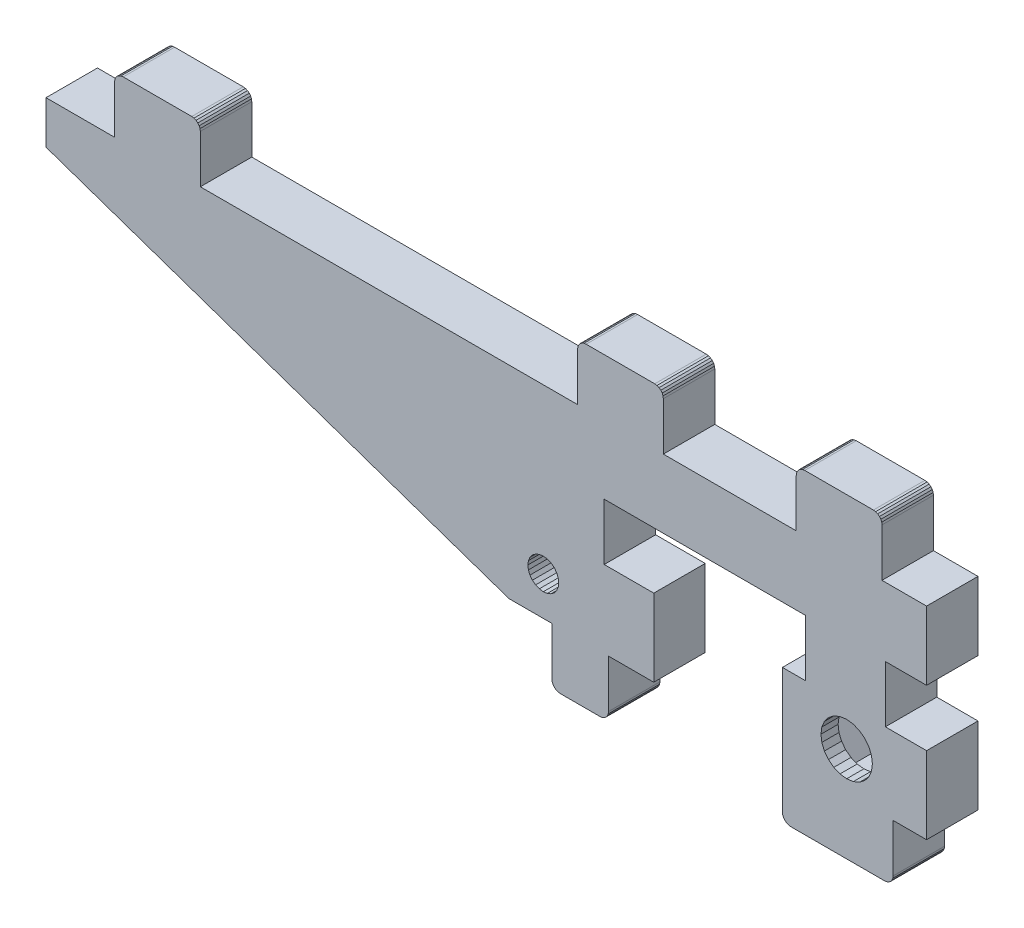
SolidWorks part; units mm, degrees
material "Maple"
ref_plane "Front Plane" through (0, 0, 0) normal (0, 0, 1) x (1, 0, 0)
ref_plane "Top Plane" through (0, 0, 0) normal (0, 1, 0) x (1, 0, 0)
ref_plane "Right Plane" through (0, 0, 0) normal (1, 0, 0) x (0, 0, -1)
sketch "Sketch1" plane through (0, 0, 0) normal (0, 0, 1) x (1, 0, 0)
  line L2259 (-418.414, -391.9409) -> (-418.7137, -392.6645)
  line L2260 (-501.1985, -368.7409) -> (-501.1985, -374.3409)
  line L2261 (-500.4573, -367.775) -> (-500.1985, -367.7409)
  line L2262 (-438.316, -397.9409) -> (-438.316, -388.9409)
  line L2263 (-451.1985, -391.6409) -> (-450.7326, -391.7022)
  line L2264 (-437.3325, -368.2409) -> (-437.4914, -368.0338)
  line L2265 (-451.6644, -391.7022) -> (-451.1985, -391.6409)
  line L2266 (-452.0985, -391.8821) -> (-451.6644, -391.7022)
  line L2267 (-406.5002, -397.9409) -> (-406.5002, -388.9447)
  line L2268 (-509.1985, -374.3409) -> (-509.1985, -379.3409)
  line L2269 (-452.7573, -394.3409) -> (-452.9372, -393.9068)
  line L2270 (-418.7137, -394.2174) -> (-418.414, -394.9409)
  line L2271 (-449.4598, -392.975) -> (-449.3985, -393.4409)
  line L2272 (-410.3985, -397.9409) -> (-410.3985, -403.5409)
  line L2273 (-450.7326, -395.1796) -> (-451.1985, -395.2409)
  line L2274 (-452.0985, -394.9998) -> (-452.4713, -394.7137)
  line L2275 (-449.4598, -393.9068) -> (-449.6396, -394.3409)
  line L2276 (-411.3037, -388.9409) -> (-411.2985, -382.3409)
  line L2277 (-411.2985, -382.3409) -> (-406.5002, -382.3447)
  line L2278 (-450.1985, -397.9409) -> (-455.1985, -397.9409)
  line L2279 (-437.1985, -374.3409) -> (-421.6985, -374.3409)
  line L2280 (-491.1985, -368.7409) -> (-491.1985, -374.3409)
  line L2281 (-491.1985, -374.3409) -> (-447.1985, -374.3409)
  line L2282 (-413.2179, -388.9409) -> (-418.414, -388.9409)
  line L2283 (-406.5002, -388.9447) -> (-411.3037, -388.9409)
  line L2284 (-422.8108, -404.4069) -> (-423.0179, -404.248)
  line L2285 (-443.5985, -397.9409) -> (-438.316, -397.9409)
  line L2286 (-420.5985, -388.9409) -> (-420.5985, -382.3409)
  line L2287 (-509.1985, -374.3409) -> (-501.1985, -374.3409)
  line L2288 (-443.5985, -403.5409) -> (-443.5985, -397.9409)
  line L2289 (-443.5985, -403.5409) -> (-443.6326, -403.7997)
  line L2290 (-443.6326, -403.7997) -> (-443.7325, -404.0409)
  line L2291 (-443.7325, -404.0409) -> (-443.8914, -404.248)
  line L2292 (-413.2179, -397.9409) -> (-410.6198, -393.4409)
  line L2293 (-412.9182, -392.6645) -> (-413.2179, -391.9409)
  line L2294 (-452.4713, -394.7137) -> (-452.7573, -394.3409)
  line L2295 (-421.6985, -368.7409) -> (-421.6644, -368.4821)
  line L2296 (-410.5325, -404.0409) -> (-410.6914, -404.248)
  line L2297 (-410.6914, -404.248) -> (-410.8985, -404.4069)
  line L2298 (-410.8985, -404.4069) -> (-411.1397, -404.5068)
  line L2299 (-492.1985, -367.7409) -> (-500.1985, -367.7409)
  line L2300 (-411.1397, -404.5068) -> (-411.3985, -404.5409)
  line L2301 (-447.0645, -368.2409) -> (-446.9056, -368.0338)
  line L2302 (-446.9056, -368.0338) -> (-446.6985, -367.8749)
  line L2303 (-418.414, -388.9409) -> (-421.0121, -393.4409)
  line L2304 (-421.0121, -393.4409) -> (-418.414, -397.9409)
  line L2305 (-418.414, -397.9409) -> (-413.2179, -397.9409)
  line L2306 (-410.6198, -393.4409) -> (-413.2179, -388.9409)
  line L2307 (-418.414, -394.9409) -> (-417.9373, -395.5622)
  line L2308 (-417.9373, -391.3196) -> (-418.414, -391.9409)
  line L2309 (-415.816, -390.4409) -> (-416.5924, -390.5431)
  line L2310 (-415.0395, -390.5431) -> (-415.816, -390.4409)
  line L2311 (-413.2179, -391.9409) -> (-413.6946, -391.3196)
  line L2312 (-413.2179, -394.9409) -> (-412.9182, -394.2174)
  line L2313 (-413.6946, -395.5622) -> (-413.2179, -394.9409)
  line L2314 (-412.4397, -367.775) -> (-412.1985, -367.8749)
  line L2315 (-412.1985, -367.8749) -> (-411.9914, -368.0338)
  line L2316 (-411.9914, -368.0338) -> (-411.8325, -368.2409)
  line L2317 (-411.8325, -368.2409) -> (-411.7326, -368.4821)
  line L2318 (-411.7326, -368.4821) -> (-411.6985, -368.7409)
  line L2319 (-501.1985, -368.7409) -> (-501.1644, -368.4821)
  line L2320 (-452.9372, -392.975) -> (-452.7573, -392.5409)
  line L2321 (-423.0179, -404.248) -> (-423.1768, -404.0409)
  line L2322 (-423.1768, -404.0409) -> (-423.2767, -403.7997)
  line L2323 (-423.2767, -403.7997) -> (-423.3108, -403.5409)
  line L2324 (-437.2326, -368.4821) -> (-437.3325, -368.2409)
  line L2325 (-437.1985, -368.7409) -> (-437.2326, -368.4821)
  line L2326 (-437.1985, -368.7409) -> (-437.1985, -374.3409)
  line L2327 (-421.5645, -368.2409) -> (-421.4056, -368.0338)
  line L2328 (-421.4056, -368.0338) -> (-421.1985, -367.8749)
  line L2329 (-449.9056, -404.248) -> (-449.6985, -404.4069)
  line L2330 (-449.6985, -404.4069) -> (-449.4573, -404.5068)
  line L2331 (-449.1985, -404.5409) -> (-444.5985, -404.5409)
  line L2332 (-449.4573, -404.5068) -> (-449.1985, -404.5409)
  line L2333 (-437.4914, -368.0338) -> (-437.6985, -367.8749)
  line L2334 (-437.6985, -367.8749) -> (-437.9397, -367.775)
  line L2335 (-438.1985, -367.7409) -> (-446.1985, -367.7409)
  line L2336 (-437.9397, -367.775) -> (-438.1985, -367.7409)
  line L2337 (-452.9985, -393.4409) -> (-452.9372, -392.975)
  line L2338 (-444.0985, -382.3409) -> (-444.0985, -388.9409)
  line L2339 (-451.6644, -395.1796) -> (-452.0985, -394.9998)
  line L2340 (-452.9372, -393.9068) -> (-452.9985, -393.4409)
  line L2341 (-450.7326, -391.7022) -> (-450.2985, -391.8821)
  line L2342 (-509.1985, -379.3409) -> (-455.1985, -397.9409)
  line L2343 (-447.1985, -368.7409) -> (-447.1985, -374.3409)
  line L2344 (-447.1985, -368.7409) -> (-447.1644, -368.4821)
  line L2345 (-447.1644, -368.4821) -> (-447.0645, -368.2409)
  line L2346 (-422.3108, -404.5409) -> (-422.5696, -404.5068)
  line L2347 (-422.5696, -404.5068) -> (-422.8108, -404.4069)
  line L2348 (-423.3108, -403.5409) -> (-423.3108, -388.9409)
  line L2349 (-492.1985, -367.7409) -> (-491.9397, -367.775)
  line L2350 (-491.9397, -367.775) -> (-491.6985, -367.8749)
  line L2351 (-491.6985, -367.8749) -> (-491.4914, -368.0338)
  line L2352 (-491.4914, -368.0338) -> (-491.3325, -368.2409)
  line L2353 (-491.3325, -368.2409) -> (-491.2326, -368.4821)
  line L2354 (-491.2326, -368.4821) -> (-491.1985, -368.7409)
  line L2355 (-406.5002, -382.3447) -> (-406.5002, -374.3409)
  line L2356 (-411.6985, -374.3409) -> (-406.5002, -374.3409)
  line L2357 (-411.6985, -368.7409) -> (-411.6985, -374.3409)
  line L2358 (-412.6985, -367.7409) -> (-412.4397, -367.775)
  line L2359 (-412.6985, -367.7409) -> (-420.6985, -367.7409)
  line L2360 (-420.9573, -367.775) -> (-420.6985, -367.7409)
  line L2361 (-421.1985, -367.8749) -> (-420.9573, -367.775)
  line L2362 (-421.6644, -368.4821) -> (-421.5645, -368.2409)
  line L2363 (-421.6985, -374.3409) -> (-421.6985, -368.7409)
  line L2364 (-446.4573, -367.775) -> (-446.1985, -367.7409)
  line L2365 (-446.6985, -367.8749) -> (-446.4573, -367.775)
  line L2366 (-500.6985, -367.8749) -> (-500.4573, -367.775)
  line L2367 (-500.9056, -368.0338) -> (-500.6985, -367.8749)
  line L2368 (-501.0645, -368.2409) -> (-500.9056, -368.0338)
  line L2369 (-501.1644, -368.4821) -> (-501.0645, -368.2409)
  line L2370 (-450.1985, -403.5409) -> (-450.1985, -397.9409)
  line L2371 (-450.1985, -403.5409) -> (-450.1644, -403.7997)
  line L2372 (-450.1644, -403.7997) -> (-450.0645, -404.0409)
  line L2373 (-450.0645, -404.0409) -> (-449.9056, -404.248)
  line L2374 (-444.3397, -404.5068) -> (-444.5985, -404.5409)
  line L2375 (-444.0985, -404.4069) -> (-444.3397, -404.5068)
  line L2376 (-443.8914, -404.248) -> (-444.0985, -404.4069)
  line L2377 (-444.0985, -388.9409) -> (-438.316, -388.9409)
  line L2378 (-420.5985, -382.3409) -> (-444.0985, -382.3409)
  line L2379 (-423.3108, -388.9409) -> (-420.5985, -388.9409)
  line L2380 (-422.3108, -404.5409) -> (-411.3985, -404.5409)
  line L2381 (-410.4326, -403.7997) -> (-410.5325, -404.0409)
  line L2382 (-410.3985, -403.5409) -> (-410.4326, -403.7997)
  line L2383 (-410.3985, -397.9409) -> (-406.5002, -397.9409)
  line L2384 (-452.7573, -392.5409) -> (-452.4713, -392.1681)
  line L2385 (-452.4713, -392.1681) -> (-452.0985, -391.8821)
  line L2386 (-450.2985, -391.8821) -> (-449.9257, -392.1681)
  line L2387 (-449.9257, -392.1681) -> (-449.6396, -392.5409)
  line L2388 (-449.6396, -392.5409) -> (-449.4598, -392.975)
  line L2389 (-449.3985, -393.4409) -> (-449.4598, -393.9068)
  line L2390 (-449.6396, -394.3409) -> (-449.9257, -394.7137)
  line L2391 (-449.9257, -394.7137) -> (-450.2985, -394.9998)
  line L2392 (-450.2985, -394.9998) -> (-450.7326, -395.1796)
  line L2393 (-451.1985, -395.2409) -> (-451.6644, -395.1796)
  line L2394 (-418.2986, -389.1409) -> (-420.7812, -393.4409)
  line L2395 (-420.7812, -393.4409) -> (-418.2986, -397.7409)
  line L2396 (-418.2986, -397.7409) -> (-413.3334, -397.7409)
  line L2397 (-413.3334, -397.7409) -> (-410.8507, -393.4409)
  line L2398 (-410.8507, -393.4409) -> (-413.3334, -389.1409)
  line L2399 (-413.3334, -389.1409) -> (-418.2986, -389.1409)
  line L2400 (-418.1831, -389.3409) -> (-420.5502, -393.4409)
  line L2401 (-420.5502, -393.4409) -> (-418.1831, -397.5409)
  line L2402 (-418.1831, -397.5409) -> (-413.4488, -397.5409)
  line L2403 (-413.4488, -397.5409) -> (-411.0817, -393.4409)
  line L2404 (-411.0817, -393.4409) -> (-413.4488, -389.3409)
  line L2405 (-413.4488, -389.3409) -> (-418.1831, -389.3409)
  line L2406 (-413.5643, -397.3409) -> (-411.3126, -393.4409)
  line L2407 (-411.3126, -393.4409) -> (-413.5643, -389.5409)
  line L2408 (-413.5643, -389.5409) -> (-418.0676, -389.5409)
  line L2409 (-418.0676, -389.5409) -> (-420.3193, -393.4409)
  line L2410 (-420.3193, -393.4409) -> (-418.0676, -397.3409)
  line L2411 (-418.0676, -397.3409) -> (-413.5643, -397.3409)
  line L2412 (-413.6798, -389.7409) -> (-417.9522, -389.7409)
  line L2413 (-417.9522, -389.7409) -> (-420.0884, -393.4409)
  line L2414 (-420.0884, -393.4409) -> (-417.9522, -397.1409)
  line L2415 (-417.9522, -397.1409) -> (-413.6798, -397.1409)
  line L2416 (-413.6798, -397.1409) -> (-411.5436, -393.4409)
  line L2417 (-411.5436, -393.4409) -> (-413.6798, -389.7409)
  line L2418 (-411.7745, -393.4409) -> (-413.7952, -389.9409)
  line L2419 (-413.7952, -389.9409) -> (-417.8367, -389.9409)
  line L2420 (-417.8367, -389.9409) -> (-419.8574, -393.4409)
  line L2421 (-419.8574, -393.4409) -> (-417.8367, -396.9409)
  line L2422 (-417.8367, -396.9409) -> (-413.7952, -396.9409)
  line L2423 (-413.7952, -396.9409) -> (-411.7745, -393.4409)
  line L2424 (-417.7212, -396.7409) -> (-413.9107, -396.7409)
  line L2425 (-413.9107, -396.7409) -> (-412.0054, -393.4409)
  line L2426 (-412.0054, -393.4409) -> (-413.9107, -390.1409)
  line L2427 (-413.9107, -390.1409) -> (-417.7212, -390.1409)
  line L2428 (-417.7212, -390.1409) -> (-419.6265, -393.4409)
  line L2429 (-419.6265, -393.4409) -> (-417.7212, -396.7409)
  line L2430 (-414.0262, -390.3409) -> (-417.6057, -390.3409)
  line L2431 (-417.6057, -390.3409) -> (-419.3955, -393.4409)
  line L2432 (-419.3955, -393.4409) -> (-417.6057, -396.5409)
  line L2433 (-417.6057, -396.5409) -> (-414.0262, -396.5409)
  line L2434 (-414.0262, -396.5409) -> (-412.2364, -393.4409)
  line L2435 (-412.2364, -393.4409) -> (-414.0262, -390.3409)
  line L2436 (-415.816, -396.4409) -> (-415.0395, -396.3387)
  line L2437 (-416.5924, -396.3387) -> (-415.816, -396.4409)
  line L8380 (-418.7137, -392.6645) -> (-418.816, -393.4409)
  line L8381 (-414.316, -390.8428) -> (-415.0395, -390.5431)
  line L8382 (-417.9373, -395.5622) -> (-417.316, -396.039)
  line L8383 (-417.316, -396.039) -> (-416.5924, -396.3387)
  line L8384 (-418.816, -393.4409) -> (-418.7137, -394.2174)
  line L8385 (-417.316, -390.8428) -> (-417.9373, -391.3196)
  line L8386 (-416.5924, -390.5431) -> (-417.316, -390.8428)
  line L8387 (-413.6946, -391.3196) -> (-414.316, -390.8428)
  line L8388 (-412.816, -393.4409) -> (-412.9182, -392.6645)
  line L8389 (-412.9182, -394.2174) -> (-412.816, -393.4409)
  line L8390 (-414.316, -396.039) -> (-413.6946, -395.5622)
  line L8391 (-415.0395, -396.3387) -> (-414.316, -396.039)
  line L8909 (-406.3037, -388.9448) -> (-406.5002, -388.9447)
  line L8910 (-406.5002, -382.3447) -> (-406.2985, -382.3448)
  line L8911 (-452.2789, -385.2588) -> (-450.0498, -380.9509)
  line L8912 (-450.0498, -380.9509) -> (-452.2352, -380.9509)
  line L8913 (-452.2352, -380.9509) -> (-450.0498, -380.9509)
  line L8914 (-450.0498, -380.9509) -> (-452.2789, -385.2588)
  line L8915 (-452.2789, -385.2588) -> (-450.106, -385.2588)
  line L8916 (-450.106, -385.2588) -> (-452.2789, -385.2588)
extrude "Boss-Extrude1" add sketch "Sketch1" against normal blind 6 contours L2272 L2383 L2267 L2283 L2276 L2277 L2355 L2356 L2357 L2318 L2317 L2316 L2315 L2314 L2358 L2359 L2360 L2361 L2328 L2327 L2362 L2295 L2363 L2279 L2326 L2325 L2324 L2264 L2333 L2334 L2336 L2335 L2364 L2365 L2302 L2301 L2345 L2344 L2343 L2281 L2280 L2354 L2353 L2352 region at (-452.5715, -383.2518, 0)
extrude "Boss-Extrude2" add sketch "Sketch1<3>" against normal blind 2 contours L2292 L2306 L2282 L2303 L2304 L2305 L2399 L2398 L2397 L2396 L2395 L2394 | L2398 L2399 L2394 L2395 L2396 L2397 L2405 L2404 L2403 L2402 L2401 L2400 | L2404 L2405 L2400 L2401 L2402 L2403 L2411 L2410 L2409 L2408 L2407 L2406 | L2410 L2411 L2406 L2407 L2408 L2409 L2417 L2416 L2415 L2414 L2413 L2412 | L2416 L2417 L2412 L2413 L2414 L2415 L2423 L2422 L2421 L2420 L2419 L2418 | L2422 L2423 L2418 L2419 L2420 L2421 L2429 L2428 L2427 L2426 L2425 L2424 | L2428 L2429 L2424 L2425 L2426 L2427 L2435 L2434 L2433 L2432 L2431 L2430 | L2434 L2435 L2430 L2431 L2432 L2433 L8391 L2436 L2437 L8383 L8382 L2307 L2270 L8384 L8380 L2259 L2308 L8385 L8386 L2309 L2310 L8381 L8387 L2311 L2293 L8388 L8389 L2312 L2313 L8390 region at (-412.0379, -391.2596, 0) region at (-415.816, -389.2723, 0) region at (-415.816, -389.4662, 0) region at (-415.816, -397.2218, 0) region at (-412.7096, -391.6474, 0) region at (-412.8775, -395.1374, 0) region at (-418.5865, -395.0405, 0) region at (-413.2133, -391.9383, 0)
sketch "Sketch1<3>" plane through (0, 0, 0) normal (0, 0, 1) x (1, 0, 0) same geometry as "Sketch1"
